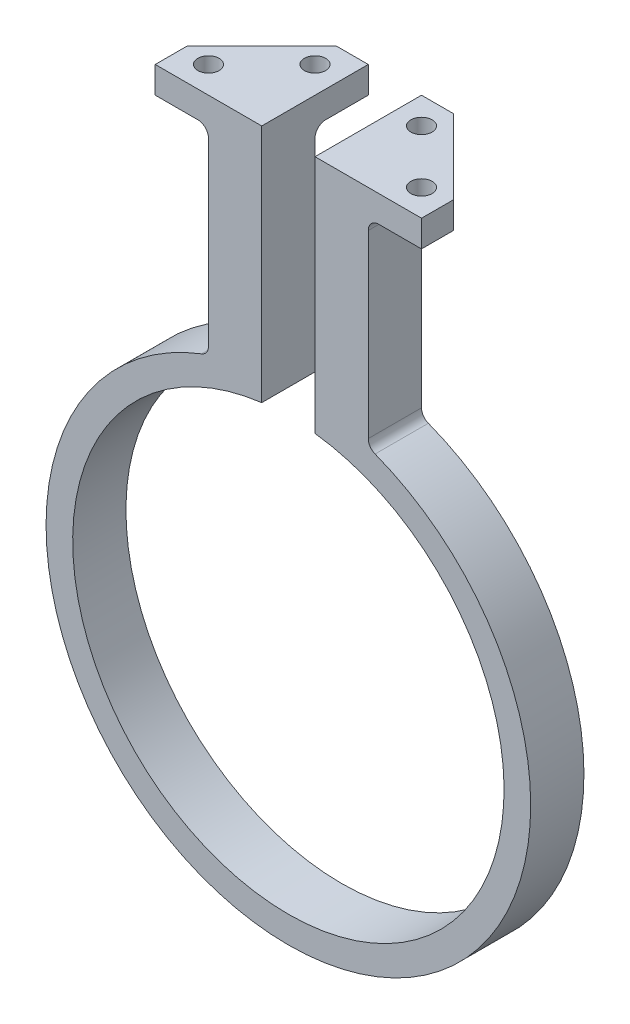
SolidWorks part; units mm, degrees
ref_plane "Front Plane" through (0, 0, 0) normal (0, 0, 1) x (1, 0, 0)
ref_plane "Top Plane" through (0, 0, 0) normal (0, 1, 0) x (1, 0, 0)
ref_plane "Right Plane" through (0, 0, 0) normal (1, 0, 0) x (0, 0, -1)
sketch "Sketch1" plane through (0, 0, 0) normal (0, 0, 1) x (1, 0, 0)
  line L0 (-6.35, 51.0415) -> (-6.35, 101.8415)
  line L1 (6.35, 51.0415) -> (6.35, 101.8415)
  line L2 (-19.05, 54.5546) -> (-19.05, 101.8415)
  line L3 (19.05, 54.5546) -> (19.05, 101.8415)
  line L4 (-19.05, 101.8415) -> (-6.35, 101.8415)
  line L5 (6.35, 101.8415) -> (19.05, 101.8415)
  arc A0 (-6.35, 51.0415) -> (6.35, 51.0415) centre (0, 0) ccw
  arc A1 (-19.05, 54.5546) -> (19.05, 54.5546) centre (0, 0) ccw
  dimension "D1" = 102.87
  dimension "D2" = 6.35
  dimension "D3" = 6.35
  dimension "D4" = 6.35
  dimension "D5" = 50.8
  dimension "D6" = 12.7
  dimension "D7" = 12.7
extrude "Boss-Extrude1" add sketch "Sketch1" along normal blind 12.7
sketch "Sketch2" plane through (0, 101.8415, 0) normal (0, 1, 0) x (1, 0, 0)
  line L0 (-6.35, -12.7) -> (-6.35, 0) construction
  line L1 (-31.75, 12.7) -> (-6.35, 12.7)
  line L2 (-31.75, 12.7) -> (-31.75, -12.7)
  line L3 (-31.75, -12.7) -> (-6.35, -12.7)
  line L4 (-6.35, 12.7) -> (-6.35, -12.7)
  line L8 (-6.35, -12.7) -> (-19.05, -12.7) construction
  circle A0 centre (-25.4, -6.35) radius 2.54
  circle A1 centre (-12.7, 6.35) radius 2.54
  dimension "D2" = 5.08
  dimension "D6" = 5.08
  dimension "D1" = 19.05
  dimension "D3" = 25.4
  dimension "D4" = 25.4
  dimension "D5" = 6.35
  dimension "D7" = 6.35
  dimension "D8" = 19.05
extrude "Boss-Extrude2" add sketch "Sketch2" along normal blind 6.35
mirror "Mirror5" about plane through (0, 0, 0) normal (1, 0, 0) of "Boss-Extrude2"
chamfer "Chamfer2" distance 1.27 angle 41 4 edges at (-25.4, 101.8415, 8.89) (25.4, 101.8415, 8.89) (-12.7, 101.8415, -3.81) (12.7, 101.8415, -3.81) first distance on face at (-25.4, 108.1915, 8.89) first distance on face at (25.4, 101.8415, 8.89) first distance on face at (-12.7, 108.1915, -3.81)
chamfer "Chamfer3" distance 17.78 angle 45 2 edges at (31.75, 105.0165, -12.7) (-31.75, 105.0165, -12.7)
fillet "Fillet3" radius 2.54 6 edges at (19.05, 54.5546, 6.35) (-19.05, 54.5546, 6.35) (-19.05, 101.8415, 6.35) (-12.7, 101.8415, 0) (12.7, 101.8415, 0) (19.05, 101.8415, 6.35)
